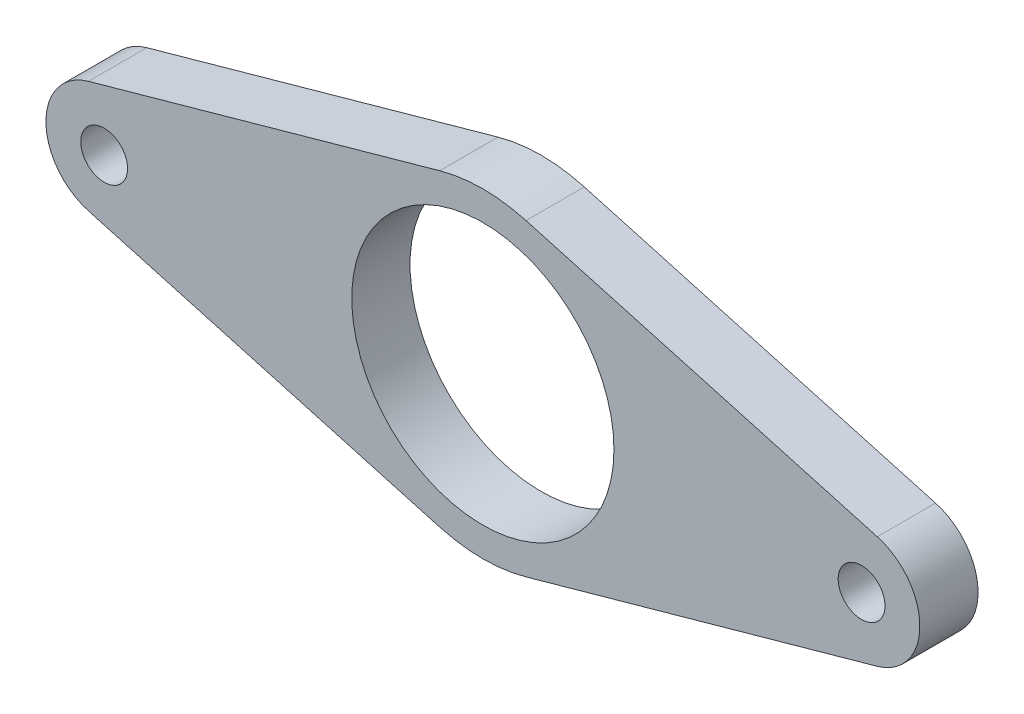
SolidWorks part; units mm, degrees
material "6061-T6 (SS)"
ref_plane "Front Plane" through (0, 0, 0) normal (0, 0, 1) x (1, 0, 0)
ref_plane "Top Plane" through (0, 0, 0) normal (0, 1, 0) x (1, 0, 0)
ref_plane "Right Plane" through (0, 0, 0) normal (1, 0, 0) x (0, 0, -1)
sketch "Sketch1" plane through (0, 0, 0) normal (0, 0, 1) x (1, 0, 0)
  line L0 (-42.9846, 6.1155) -> (-4.7014, 16.8177)
  line L1 (-42.9846, -6.1155) -> (-4.7014, -16.8177)
  line L2 (42.9846, -6.1155) -> (4.7014, -16.8177)
  line L3 (42.9846, 6.1155) -> (4.7014, 16.8177)
  arc A0 (-4.7014, -16.8177) -> (4.7014, -16.8177) centre (0, 0) ccw
  circle A1 centre (-41.275, 0) radius 2.5527
  circle A2 centre (41.275, 0) radius 2.5527
  circle A3 centre (0, 0) radius 14.2875
  arc A4 (-42.9846, 6.1155) -> (-42.9846, -6.1155) centre (-41.275, 0) ccw
  arc A5 (42.9846, 6.1155) -> (42.9846, -6.1155) centre (41.275, 0) cw
  arc A6 (4.7014, 16.8177) -> (-4.7014, 16.8177) centre (0, 0) ccw
  dimension "D1" = 28.575
  dimension "D2" = 5.1054
  dimension "D3" = 34.925
  dimension ".25" = 6.35
  dimension "D4" = 41.275
  dimension "D5" = 41.275
extrude "Boss-Extrude1" add sketch "Sketch1" along normal blind 6.35 contours L3 A6 L0 A4 L1 A0 L2 A5 A1 A2 A3 region at (-23.5699, 10.4896, 0)
